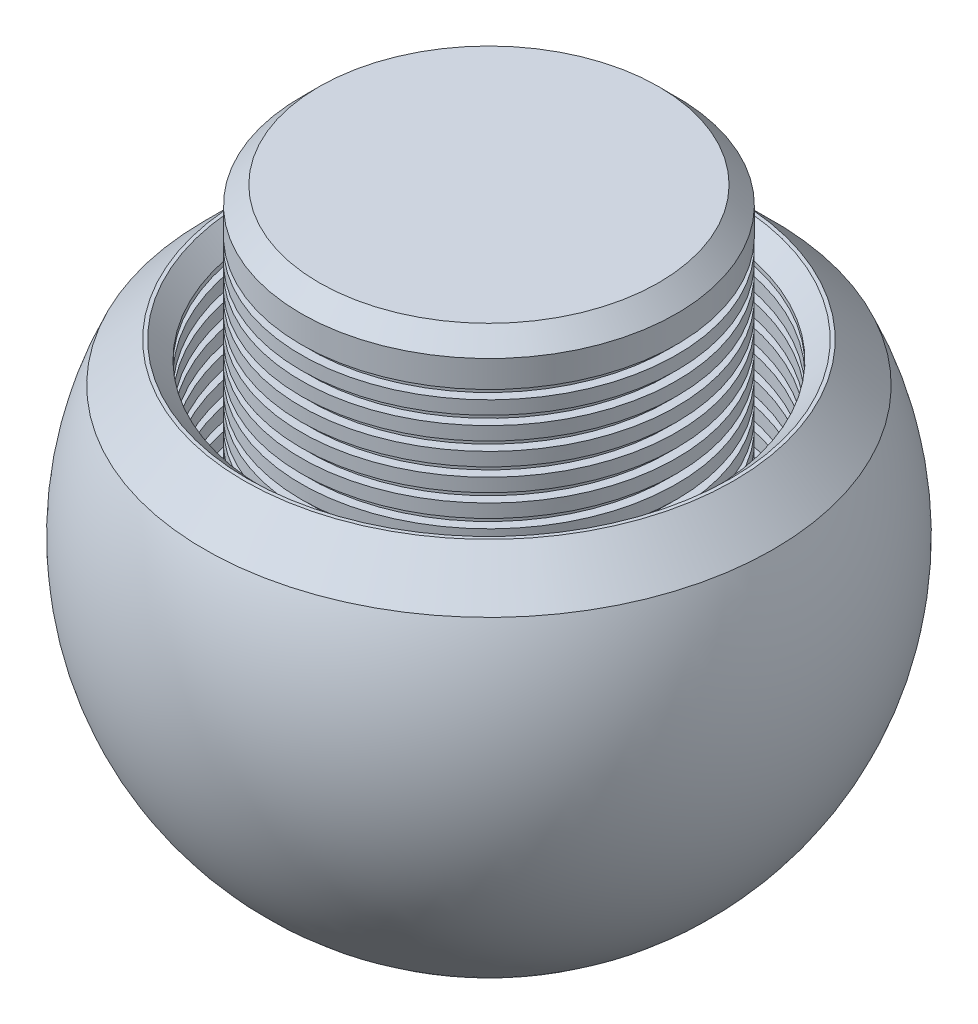
SolidWorks part; units mm, degrees
ref_plane "Front Plane" through (0, 0, 0) normal (0, 0, 1) x (1, 0, 0)
ref_plane "Top Plane" through (0, 0, 0) normal (0, 1, 0) x (1, 0, 0)
ref_plane "Right Plane" through (0, 0, 0) normal (1, 0, 0) x (0, 0, -1)
sketch "Sketch1" plane through (0, 0, 0) normal (0, 0, 1) x (1, 0, 0)
  line L0 (0, -1050.8) -> (0, -15) construction
  line L1 (0, -15) -> (0, 17)
  line L2 (0, 17) -> (10.5, 17)
  line L3 (10.5, 17) -> (10.5, -5)
  line L4 (10.5, -5) -> (12.5, -5)
  line L5 (12.5, -5) -> (12.5, 9.5)
  line L6 (12.5, 9.5) -> (14.6969, 9.5)
  line L7 (0, -15) -> (9.0139, -15)
  line L8 (0, -15) -> (0, 14.9124) construction
  arc A0 (9.0139, -15) -> (14.6969, 9.5) centre (0, 0) ccw
  point P1 (17.8049, 9.5)
  point P2 (0, -22.0937)
  point P10 (14.742, 9.5)
  dimension "D6" = 17.5
  dimension "D1" = 7.5
  dimension "D2" = 21
  dimension "D3" = 25
  dimension "D4" = 22
  dimension "D5" = 17
  dimension "D7" = 10
revolve "Revolve1" add sketch "Sketch1" angle 360 about L8
chamfer "Chamfer1" distance 1 angle 45 3 edges at (0, 9.5, -12.5) (0, 17, -10.5) (0, 9.5, -14.6969) first distance on face at (0, -5, -12.5) first distance on face at (0, 17, -10.5) first distance on face at (0, 9.5, -12.5)
sketch "Sketch2" plane through (0, 0, 0) normal (0, 0, 1) x (1, 0, 0)
  line L0 (12.5, 8.5) -> (-12.5, 8.5) construction
  line L1 (-10.5, 16) -> (10.5, 16) construction
  line L2 (12.5, 8.5) -> (-12.5, 8.5) construction
  line L3 (-10.5, 16) -> (10.5, 16) construction
  line L4 (10.5, 16) -> (10.5, 8.5) construction
  line L5 (12.5, 7.5) -> (12.5, 16.7976) construction
  line L6 (11.5, 8.5) -> (11.5, 14.25) construction
  line L7 (10.5, 16) -> (12.5, 16) construction
  line L8 (0, 0) -> (0, 29.4171) construction
  line L9 (13, 14.5) -> (10, 14.5)
  line L10 (13, 14.5) -> (13, 14)
  line L11 (13, 14) -> (10, 14)
  line L12 (10, 14.5) -> (10, 14)
  line L13 (13, 14.5) -> (10, 14) construction
  line L14 (13, 14) -> (10, 14.5) construction
  point P9 (11.5, 16)
  dimension "D1" = 0.5
  dimension "D2" = 1.5
  dimension "D3" = 3
revolve "Cut-Revolve1" cut sketch "Sketch2" angle 360 about L8
pattern_linear "LPattern1" count 15 spacing 1.25 along (0, -1, 0) of "Cut-Revolve1"
